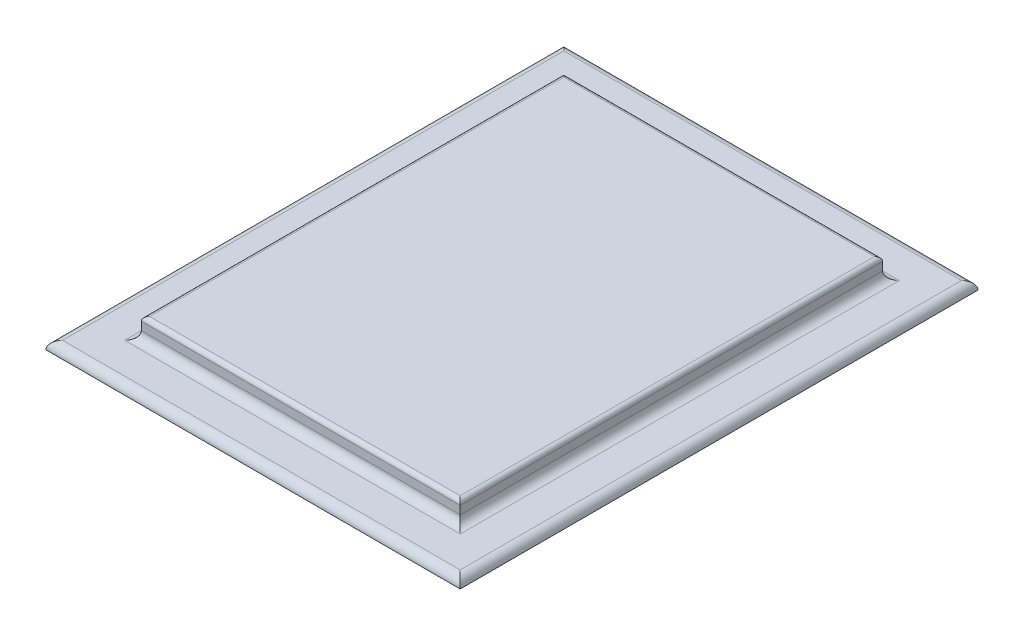
SolidWorks part; units mm, degrees
ref_plane "Front Plane" through (0, 0, 0) normal (0, 0, 1) x (1, 0, 0)
ref_plane "Top Plane" through (0, 0, 0) normal (0, 1, 0) x (1, 0, 0)
ref_plane "Right Plane" through (0, 0, 0) normal (1, 0, 0) x (0, 0, -1)
sketch "Sketch1" plane through (0, 0, 0) normal (0, 1, 0) x (1, 0, 0)
  line L1 (2.3856, 13.1127) -> (22.3856, 13.1127)
  line L2 (2.3856, 13.1127) -> (2.3856, -11.8873)
  line L3 (2.3856, -11.8873) -> (22.3856, -11.8873)
  line L4 (22.3856, 13.1127) -> (22.3856, -11.8873)
  dimension "D1" = 25
  dimension "D2" = 20
extrude "Boss-Extrude1" add sketch "Sketch1" along normal blind 0.4
sketch "Sketch4" plane through (0, 0.4, 0) normal (0, 1, 0) x (1, 0, 0)
  line L0 (12.3856, -11.8873) -> (12.3856, 13.1127) construction
  line L1 (2.3856, -11.8873) -> (22.3856, -11.8873) construction
  line L2 (22.3856, 13.1127) -> (2.3856, 13.1127) construction
  line L3 (22.3856, 0.6127) -> (2.3856, 0.6127) construction
  line L4 (22.3856, -11.8873) -> (22.3856, 13.1127) construction
  line L5 (2.3856, 13.1127) -> (2.3856, -11.8873) construction
  line L7 (20.0856, -9.5873) -> (4.6856, -9.5873)
  line L8 (20.0856, -9.5873) -> (20.0856, 10.8127)
  line L9 (20.0856, 10.8127) -> (4.6856, 10.8127)
  line L10 (4.6856, -9.5873) -> (4.6856, 10.8127)
  line L11 (20.0856, -9.5873) -> (4.6856, 10.8127) construction
  line L12 (20.0856, 10.8127) -> (4.6856, -9.5873) construction
  point P12 (12.3856, 0.6127)
  dimension "D1" = 20.4
  dimension "D2" = 15.4
extrude "Boss-Extrude3" add sketch "Sketch4" along normal blind 1
sketch "Sketch5" plane through (0, 0, 0) normal (0, -1, 0) x (1, 0, 0)
  line L7 (19.8856, 9.3873) -> (4.8856, 9.3873)
  line L8 (19.8856, 9.3873) -> (19.8856, -10.6127)
  line L9 (19.8856, -10.6127) -> (4.8856, -10.6127)
  line L10 (4.8856, 9.3873) -> (4.8856, -10.6127)
  line L11 (19.8856, 9.3873) -> (4.8856, -10.6127) construction
  line L12 (19.8856, -10.6127) -> (4.8856, 9.3873) construction
  point P12 (12.3856, -0.6127)
  dimension "D1" = 15
  dimension "D2" = 20
extrude "Cut-Extrude1" cut sketch "Sketch5" against normal blind 1 contours L7 L10 L9 L8
fillet "Fillet3" radius 0.4 4 edges at (20.0856, 0.4, -0.6127) (12.3856, 0.4, 9.5873) (4.6856, 0.4, -0.6127) (12.3856, 0.4, -10.8127)
fillet "Fillet4" radius 0.2 4 edges at (12.3856, 1.4, -10.8127) (20.0856, 1.4, -0.6127) (12.3856, 1.4, 9.5873) (4.6856, 1.4, -0.6127)
fillet "Fillet5" radius 0.5 4 edges at (12.3856, 1, 9.3873) (19.8856, 1, -0.6127) (4.8856, 1, -0.6127) (12.3856, 1, -10.6127)
fillet "Fillet6" radius 0.4 4 edges at (12.3856, 0.4, 11.8873) (2.3856, 0.4, -0.6127) (22.3856, 0.4, -0.6127) (12.3856, 0.4, -13.1127)
